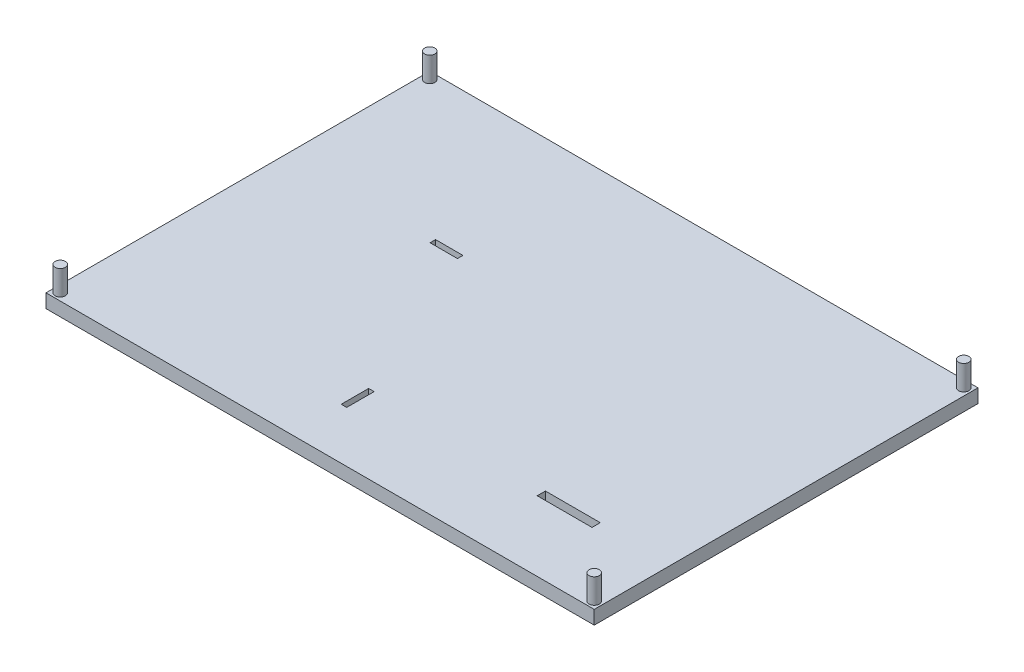
SolidWorks part; units mm, degrees
ref_plane "Front Plane" through (0, 0, 0) normal (0, 0, 1) x (1, 0, 0)
ref_plane "Top Plane" through (0, 0, 0) normal (0, 1, 0) x (1, 0, 0)
ref_plane "Right Plane" through (0, 0, 0) normal (1, 0, 0) x (0, 0, -1)
sketch "Sketch1" plane through (0, 0, 0) normal (0, 1, 0) x (1, 0, 0)
  line L1 (-127, -88.9) -> (127, -88.9)
  line L2 (-127, -88.9) -> (-127, 88.9)
  line L3 (-127, 88.9) -> (127, 88.9)
  line L4 (127, -88.9) -> (127, 88.9)
  line L5 (-127, -88.9) -> (127, 88.9) construction
  line L6 (-127, 88.9) -> (127, -88.9) construction
  point P0 (0, 0)
  dimension "D1" = 254
  dimension "D2" = 177.8
extrude "Boss-Extrude1" add sketch "Sketch1" along normal blind 6.35
sketch "Sketch2" plane through (0, 6.35, 0) normal (0, 1, 0) x (1, 0, 0)
  line L0 (127, 88.9) -> (-127, 88.9) construction
  line L1 (-127, 88.9) -> (-127, -88.9) construction
  line L2 (127, -88.9) -> (127, 88.9) construction
  line L3 (-127, -88.9) -> (127, -88.9) construction
  circle A0 centre (-123.698, -85.598) radius 2.3813
  circle A1 centre (-123.698, 85.598) radius 2.3813
  circle A2 centre (123.698, 85.598) radius 2.3813
  circle A3 centre (123.698, -85.598) radius 2.3813
  point P0 (-123.698, 85.598)
  point P5 (123.698, 85.598)
  point P8 (123.698, -85.598)
  point P11 (-123.698, -85.598)
  dimension "D9" = 4.7625
  dimension "D10" = 4.7625
  dimension "D11" = 4.7625
  dimension "D12" = 4.7625
  dimension "D1" = 3.302
  dimension "D2" = 3.302
  dimension "D3" = 3.302
  dimension "D4" = 3.302
  dimension "D5" = 3.302
  dimension "D6" = 3.302
  dimension "D7" = 3.302
  dimension "D8" = 3.302
extrude "Boss-Extrude2" add sketch "Sketch2" along normal blind 11.43 contours A0 | A3 | A2 | A1
sketch "Sketch6" plane through (0, 0, 0) normal (0, -1, 0) x (1, 0, 0)
  line L0 (-127, 88.9) -> (127, 88.9) construction
  line L1 (-10.09, 66.4765) -> (-98.99, 66.4765)
  line L2 (-10.09, 66.4765) -> (-10.09, 22.0265)
  line L3 (-10.09, 22.0265) -> (-98.99, 22.0265)
  line L4 (-98.99, 66.4765) -> (-98.99, 22.0265)
  line L5 (-127, -88.9) -> (-127, 88.9) construction
  line L6 (127, 88.9) -> (127, -88.9) construction
  line L7 (93.6056, 56.5361) -> (68.2056, 56.5361)
  line L8 (93.6056, 56.5361) -> (93.6056, 52.7261)
  line L9 (93.6056, 52.7261) -> (68.2056, 52.7261)
  line L10 (68.2056, 56.5361) -> (68.2056, 52.7261)
  line L11 (93.6056, 56.5361) -> (68.2056, 52.7261) construction
  line L12 (93.6056, 52.7261) -> (68.2056, 56.5361) construction
  line L14 (-40.3547, -18.8918) -> (-63.2147, -18.8918)
  line L15 (-40.3547, -18.8918) -> (-40.3547, -51.9118)
  line L16 (-40.3547, -51.9118) -> (-63.2147, -51.9118)
  line L17 (-63.2147, -18.8918) -> (-63.2147, -51.9118)
  line L18 (-40.3547, -18.8918) -> (-63.2147, -51.9118) construction
  line L19 (-40.3547, -51.9118) -> (-63.2147, -18.8918) construction
  line L20 (127, -88.9) -> (-127, -88.9) construction
  point P8 (80.9056, 54.6311)
  point P15 (-51.7847, -35.4018)
  dimension "D1" = 88.9
  dimension "D2" = 44.45
  dimension "D3" = 22.4235
  dimension "D4" = 28.01
  dimension "D5" = 25.4
  dimension "D6" = 3.81
  dimension "D7" = 33.3944
  dimension "D8" = 32.3639
  dimension "D9" = 33.02
  dimension "D10" = 22.86
  dimension "D11" = 75.2153
  dimension "D12" = 36.9882
extrude "Cut-Extrude1" cut sketch "Sketch6" against normal blind 3.81
sketch "Sketch7" plane through (0, 3.81, 0) normal (0, -1, 0) x (-1, 0, 0)
  line L0 (10.09, -22.0265) -> (10.09, -66.4765) construction
  line L1 (-93.6056, -52.7261) -> (-68.2056, -52.7261)
  line L2 (-93.6056, -52.7261) -> (-93.6056, -56.5361)
  line L3 (-93.6056, -56.5361) -> (-68.2056, -56.5361)
  line L4 (-68.2056, -52.7261) -> (-68.2056, -56.5361)
  line L5 (11.36, -65.2065) -> (13.9, -65.2065)
  line L6 (11.36, -65.2065) -> (11.36, -52.5065)
  line L7 (11.36, -52.5065) -> (13.9, -52.5065)
  line L8 (13.9, -65.2065) -> (13.9, -52.5065)
  line L9 (45.4347, 20.1618) -> (58.1347, 20.1618)
  line L10 (45.4347, 20.1618) -> (45.4347, 22.7018)
  line L11 (45.4347, 22.7018) -> (58.1347, 22.7018)
  line L12 (58.1347, 20.1618) -> (58.1347, 22.7018)
  line L13 (10.09, -66.4765) -> (98.99, -66.4765) construction
  line L14 (63.2147, 18.8918) -> (63.2147, 51.9118) construction
  line L15 (40.3547, 18.8918) -> (63.2147, 18.8918) construction
  dimension "D1" = 12.7
  dimension "D2" = 2.54
  dimension "D3" = 1.27
  dimension "D4" = 1.27
  dimension "D5" = 12.7
  dimension "D6" = 2.54
  dimension "D7" = 5.08
  dimension "D8" = 1.27
extrude "Cut-Extrude2" cut sketch "Sketch7" against normal through all
